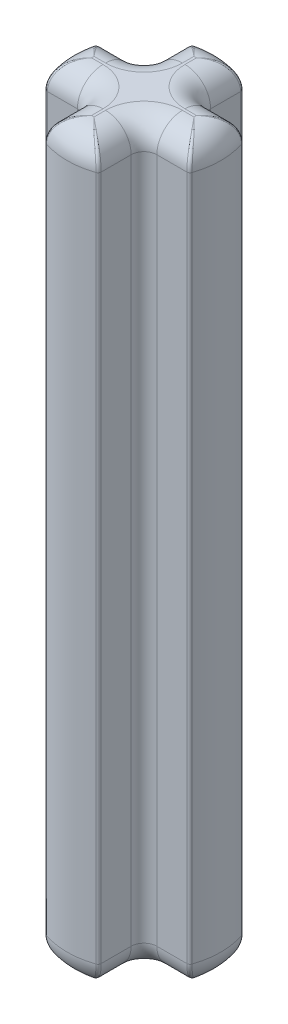
SolidWorks part; units mm, degrees
ref_plane "Front Plane" through (0, 0, 0) normal (0, 0, 1) x (1, 0, 0)
ref_plane "Top Plane" through (0, 0, 0) normal (0, 1, 0) x (1, 0, 0)
ref_plane "Right Plane" through (0, 0, 0) normal (1, 0, 0) x (0, 0, -1)
sketch "Sketch2" plane through (0, 0, 0) normal (0, 1, 0) x (1, 0, 0)
  line L0 (1.24, 0.84) -> (2.1777, 0.84)
  line L2 (-0.84, 2.1777) -> (-0.84, 1.24)
  line L4 (0.84, 2.1777) -> (0.84, 1.24)
  line L5 (-0.84, 2.2482) -> (0.84, -2.2482) construction
  line L6 (-0.84, -2.2482) -> (0.84, 2.2482) construction
  line L7 (-2.1777, 0.84) -> (-1.24, 0.84)
  line L9 (-2.1777, -0.84) -> (-1.24, -0.84)
  line L11 (-2.2482, 0.84) -> (2.2482, -0.84) construction
  line L12 (-2.2482, -0.84) -> (2.2482, 0.84) construction
  line L13 (1.24, -0.84) -> (2.1777, -0.84)
  line L14 (-0.84, -1.24) -> (-0.84, -2.1777)
  line L15 (0.84, -1.24) -> (0.84, -2.1777)
  arc A0 (-0.7722, -2.2724) -> (0.7722, -2.2724) centre (0, 0) ccw
  arc A1 (2.2724, -0.7722) -> (2.2724, 0.7722) centre (0, 0) ccw
  arc A2 (0.7722, 2.2724) -> (-0.7722, 2.2724) centre (0, 0) ccw
  arc A3 (-2.2724, 0.7722) -> (-2.2724, -0.7722) centre (0, 0) ccw
  arc A4 (0.7722, -2.2724) -> (0.84, -2.1777) centre (0.74, -2.1777) ccw
  arc A5 (-0.84, -2.1777) -> (-0.7722, -2.2724) centre (-0.74, -2.1777) ccw
  arc A6 (2.1777, -0.84) -> (2.2724, -0.7722) centre (2.1777, -0.74) ccw
  arc A7 (2.1777, 0.84) -> (2.2724, 0.7722) centre (2.1777, 0.74) cw
  arc A8 (-2.2724, -0.7722) -> (-2.1777, -0.84) centre (-2.1777, -0.74) ccw
  arc A9 (-2.1777, 0.84) -> (-2.2724, 0.7722) centre (-2.1777, 0.74) ccw
  arc A10 (0.7722, 2.2724) -> (0.84, 2.1777) centre (0.74, 2.1777) cw
  arc A11 (-0.7722, 2.2724) -> (-0.84, 2.1777) centre (-0.74, 2.1777) ccw
  arc A12 (-1.24, -0.84) -> (-0.84, -1.24) centre (-1.24, -1.24) cw
  arc A13 (1.24, -0.84) -> (0.84, -1.24) centre (1.24, -1.24) ccw
  arc A14 (1.24, 0.84) -> (0.84, 1.24) centre (1.24, 1.24) cw
  arc A15 (-1.24, 0.84) -> (-0.84, 1.24) centre (-1.24, 1.24) ccw
  point P40 (-0.84, -0.84)
  point P43 (0.84, -0.84)
  dimension "D1" = 4.8
  dimension "D4" = 0.1
  dimension "D5" = 0.4
  dimension "D2" = 1.68
  dimension "D3" = 1.68
extrude "Boss-Extrude3" add sketch "Sketch2" along normal blind 23
fillet "Fillet1" radius 0.8 24 edges at (0.8213, 0, -2.2359) (0.84, 0, -1.7089) (0.9572, 0, -0.9572) (1.7089, 0, -0.84) (2.2359, 0, -0.8213) (2.4, 0, 0) (2.2359, 0, 0.8213) (1.7089, 0, 0.84) (0.9572, 0, 0.9572) (0.84, 0, 1.7089) (0.8213, 0, 2.2359) (0, 0, 2.4) (-0.8213, 0, 2.2359) (-0.84, 0, 1.7089) (-0.9572, 0, 0.9572) (-1.7089, 0, 0.84) (-2.2359, 0, 0.8213) (-2.4, 0, 0) (-2.2359, 0, -0.8213) (-1.7089, 0, -0.84) (-0.9572, 0, -0.9572) (-0.84, 0, -1.7089) (-0.8213, 0, -2.2359) (0, 0, -2.4)
fillet "Fillet2" radius 0.8 24 edges at (0.8213, 23, -2.2359) (0.84, 23, -1.7089) (0.9572, 23, -0.9572) (1.7089, 23, -0.84) (2.2359, 23, -0.8213) (2.4, 23, 0) (2.2359, 23, 0.8213) (1.7089, 23, 0.84) (0.9572, 23, 0.9572) (0.84, 23, 1.7089) (0.8213, 23, 2.2359) (0, 23, 2.4) (-0.8213, 23, 2.2359) (-0.84, 23, 1.7089) (-0.9572, 23, 0.9572) (-1.7089, 23, 0.84) (-2.2359, 23, 0.8213) (-2.4, 23, 0) (-2.2359, 23, -0.8213) (-1.7089, 23, -0.84) (-0.9572, 23, -0.9572) (-0.84, 23, -1.7089) (-0.8213, 23, -2.2359) (0, 23, -2.4)
